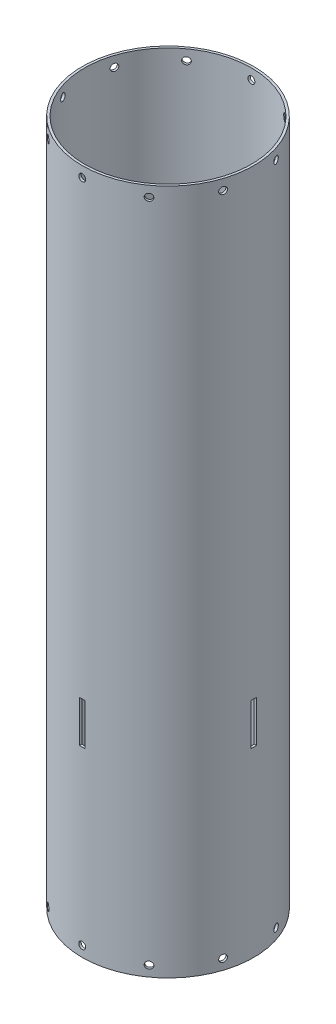
SolidWorks part; units mm, degrees
material "Fiberglass"
ref_plane "Front Plane" through (0, 0, 0) normal (0, 0, 1) x (1, 0, 0)
ref_plane "Top Plane" through (0, 0, 0) normal (0, 1, 0) x (1, 0, 0)
ref_plane "Right Plane" through (0, 0, 0) normal (1, 0, 0) x (0, 0, -1)
sketch "Sketch1" plane through (0, 0, 0) normal (0, 1, 0) x (1, 0, 0)
  circle A0 centre (0, 0) radius 76.2
  circle A1 centre (0, 0) radius 78.359
  dimension "D1" = 152.4
  dimension "D2" = 156.718
extrude "Boss-Extrude1" add sketch "Sketch1" along normal blind 626.11
sketch "Sketch2" plane through (0, 0, 0) normal (0, 0, 1) x (1, 0, 0)
  line L0 (0, 0) -> (0, 105.6712) construction
  line L1 (-76.2, 0) -> (76.2, 0) construction
  line L2 (-78.359, 0) -> (78.359, 0) construction
  line L3 (78.359, 313.055) -> (42.8908, 313.055) construction
  line L4 (78.359, 0) -> (78.359, 626.11) construction
  circle A0 centre (0, 9.525) radius 3.175
  circle A1 centre (0, 616.585) radius 3.175
  dimension "D1" = 6.35
  dimension "D2" = 9.525
extrude "Cut-Extrude1" cut sketch "Sketch2" against normal through all
ref_axis "Axis1" through (0, 0, 0) along (0, 1, 0)
pattern_circular "CirPattern1" count 10 over 360 about axis through (0, 0, 0) along (0, 1, 0) of "Cut-Extrude1" reverse direction yes
sketch "Sketch3" plane through (0, 0, 0) normal (0, 0, 1) x (1, 0, 0)
  line L0 (0, 0) -> (0, 105.6712) construction
  line L1 (-2.54, 166.37) -> (2.54, 166.37)
  line L2 (-2.54, 166.37) -> (-2.54, 204.47)
  line L3 (-2.54, 204.47) -> (2.54, 204.47)
  line L4 (2.54, 166.37) -> (2.54, 204.47)
  line L5 (-2.54, 166.37) -> (2.54, 204.47) construction
  line L6 (-2.54, 204.47) -> (2.54, 166.37) construction
  line L7 (-76.2, 0) -> (76.2, 0) construction
  line L8 (0, 626.11) -> (0, 408.1695) construction
  line L9 (76.2, 626.11) -> (-76.2, 626.11) construction
  point P0 (0, 185.42)
  dimension "D1" = 166.37
  dimension "D2" = 38.1
  dimension "D3" = 5.08
extrude "Cut-Extrude2" cut sketch "Sketch3" against normal through all
ref_axis "Axis2" through (0, 626.11, 0) along (0, -1, 0)
pattern_circular "CirPattern2" count 4 over 360 about axis through (0, 626.11, 0) along (0, -1, 0) of "Cut-Extrude2"
